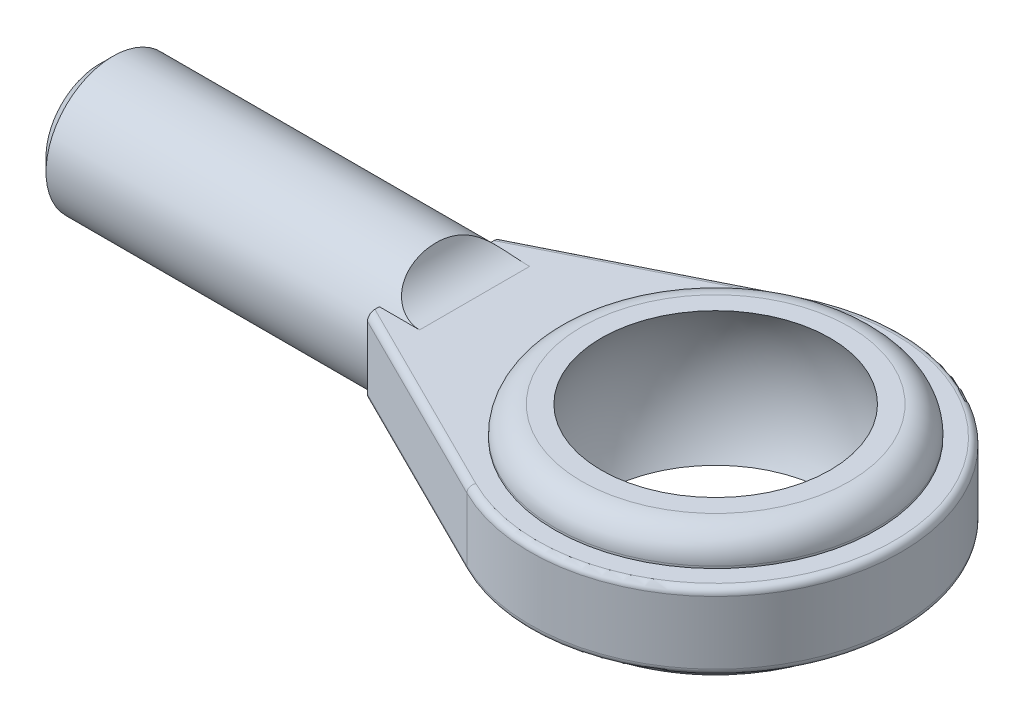
SolidWorks part; units mm, degrees
material "AISI 304"
ref_plane "Front Plane" through (0, 0, 0) normal (0, 0, 1) x (1, 0, 0)
ref_plane "Top Plane" through (0, 0, 0) normal (0, 1, 0) x (1, 0, 0)
ref_plane "Right Plane" through (0, 0, 0) normal (1, 0, 0) x (0, 0, -1)
sketch "Sketch1" plane through (0, 0, 0) normal (1, 0, 0) x (0, 0, -1)
  circle A0 centre (0, 0) radius 5
  dimension "D1" = 10
extrude "Boss-Extrude1" add sketch "Sketch1" along normal blind 25
chamfer "Chamfer1" distance 1 angle 45 1 edges at (0, 0, -5)
sketch "Sketch2" plane through (0, 0, 0) normal (0, 1, 0) x (1, 0, 0)
  line L0 (39.8163, 12.3929) -> (25, 5)
  line L1 (25, 5) -> (25, -5)
  line L2 (25, -5) -> (39.8163, -12.3929)
  circle A0 centre (46, 0) radius 13.85
  dimension "D1" = 27.7
  dimension "D2" = 21
extrude "Boss-Extrude2" add sketch "Sketch2" along normal mid plane 5.7 contours A0 L0 L1 L2 | A0 region at (29.8815, 0, 0) region at (46, 0, 0)
fillet "Fillet1" radius 0.5 6 edges at (32.4081, -2.85, 8.6965) (59.85, -2.85, 0) (32.4081, 2.85, -8.6965) (59.85, 2.85, 0) (32.4081, -2.85, -8.6965) (32.4081, 2.85, 8.6965)
fillet "Fillet2" radius 3 2 edges at (25, -2.85, 0) (25, 2.85, 0)
sketch "Sketch5" plane through (0, 0, 0) normal (0, 1, 0) x (1, 0, 0)
  circle A0 centre (46, 0) radius 12
  dimension "D1" = 24
extrude "Boss-Extrude3" add sketch "Sketch5" along normal mid plane 10
fillet "Fillet3" radius 2 2 edges at (46, -5, 12) (46, 5, 12)
sketch "Sketch4" plane through (0, 0, 0) normal (0, 1, 0) x (1, 0, 0)
  line L0 (46, 9.9) -> (46, -9.9)
  arc A0 (46, -9.9) -> (46, 9.9) centre (46, 0) ccw
  dimension "D1" = 19.8
revolve "Cut-Revolve1" cut sketch "Sketch4" angle 360 about L0
ref_plane "Plane1" through (0, 0, 0) normal (0, 1, 0) x (1, 0, 0)
sketch "Sketch6" plane through (0, 0, 0) normal (0, 1, 0) x (1, 0, 0)
  point P0 (46, 0)
sketch "Sketch7" plane through (0, 0, 0) normal (0, 1, 0) x (1, 0, 0)
  point P0 (0, 0)
